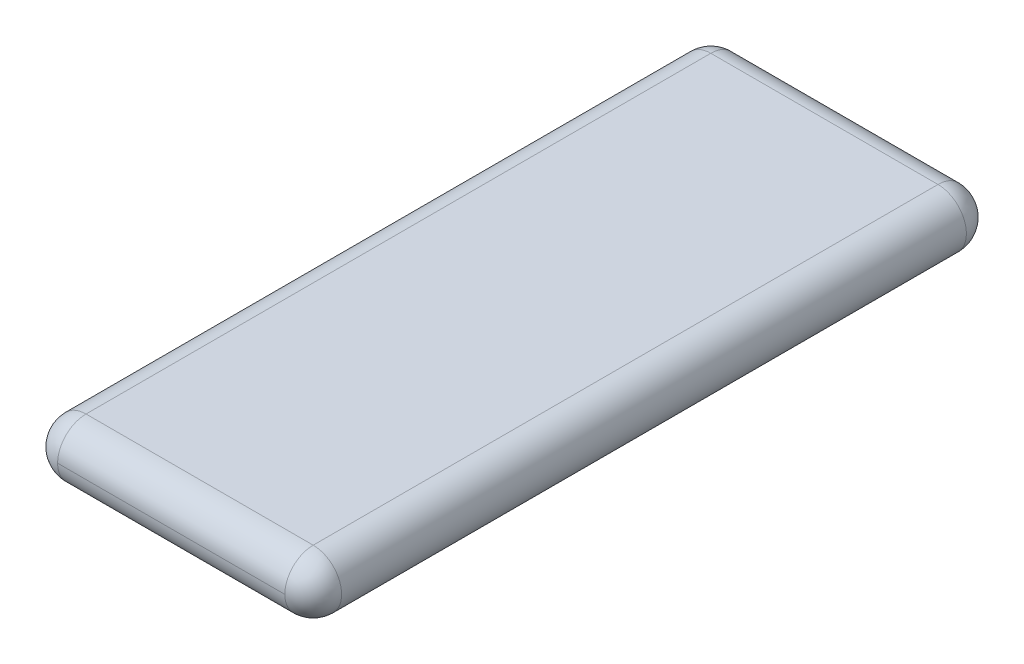
SolidWorks part; units mm, degrees
ref_plane "Front Plane" through (0, 0, 0) normal (0, 0, 1) x (1, 0, 0)
ref_plane "Top Plane" through (0, 0, 0) normal (0, 1, 0) x (1, 0, 0)
ref_plane "Right Plane" through (0, 0, 0) normal (1, 0, 0) x (0, 0, -1)
sketch "Sketch1" plane through (0, 0, 0) normal (0, 0, 1) x (1, 0, 0)
  line L0 (0, 0) -> (40, 0) construction
  line L1 (0, 5) -> (40, 5)
  line L2 (0, -5) -> (40, -5)
  arc A0 (0, 5) -> (0, -5) centre (0, 0) ccw
  arc A1 (40, -5) -> (40, 5) centre (40, 0) ccw
  point P3 (20, 0)
  dimension "D1" = 40
  dimension "D2" = 10
extrude "Boss-Extrude1" add sketch "Sketch1" along normal blind 120
fillet "Fillet1" radius 5 8 edges at (20, -5, 0) (45, 0, 0) (20, 5, 0) (-5, 0, 0) (20, 5, 120) (45, 0, 120) (20, -5, 120) (-5, 0, 120)
